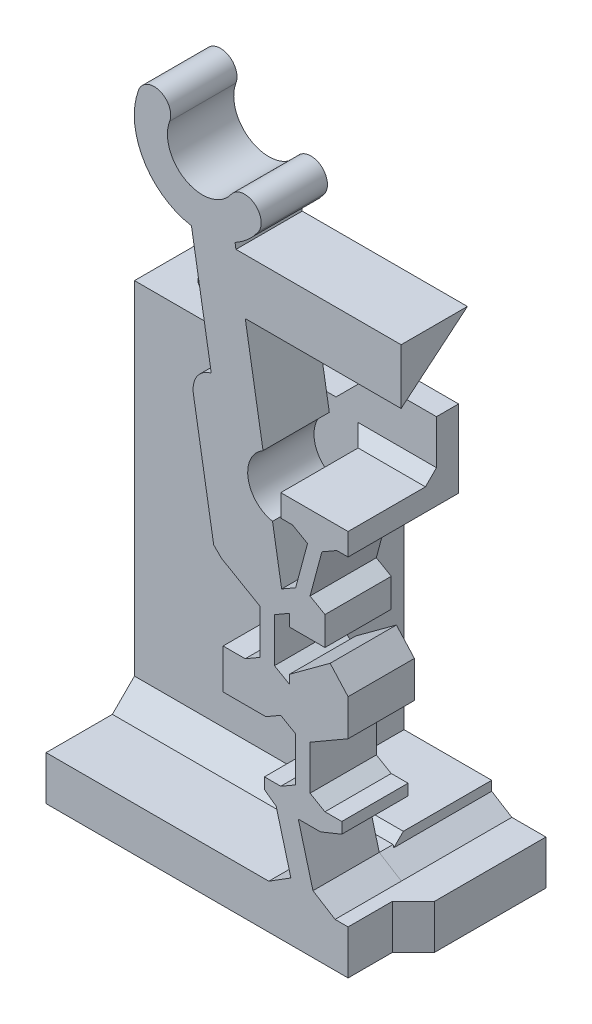
SolidWorks part; units mm, degrees
material "Nylon 6/12"
ref_plane "Front Plane" through (0, 0, 0) normal (0, 0, 1) x (1, 0, 0)
ref_plane "Top Plane" through (0, 0, 0) normal (0, 1, 0) x (1, 0, 0)
ref_plane "Right Plane" through (0, 0, 0) normal (1, 0, 0) x (0, 0, -1)
sketch "Sketch-SkeletonConfigUp" plane through (0, 0, 0) normal (0, 0, 1) x (1, 0, 0)
  line L0 (0, 0) -> (0, -50000) construction
  line L1 (0, 0) -> (4.5811, 6.2164) construction
  line L2 (9.8143, 13.3177) -> (4.5811, 13.945) construction
  line L3 (4.5811, 13.945) -> (2.9713, 10.4094) construction
  line L4 (2.9713, 10.4094) -> (4.5811, 6.2164) construction
  line L5 (4.5811, 13.945) -> (6.2429, 19.1409) construction
  line L6 (2.9713, 10.4094) -> (0.0405, 27.8193) construction
  line L7 (4.5811, 6.2164) -> (9.8143, 13.3177) construction
  line L8 (-587.3593, -797.0242) -> (9.8143, 13.3177) construction
  dimension "D2" = 7.7221
  dimension "D3" = 8.8212
  dimension "D4" = 5.2707
  dimension "D5" = 119.553
  dimension "D6" = 3.8848
  dimension "D7" = 5.4552
  dimension "D8" = 17.6549
  dimension "D9" = 4.4914
  dimension "D10" = 6.745
  dimension "D11" = 145.964
  dimension "D12" = 143.612
sketch "Sketch-SkeletonConfigDown" plane through (0, 0, 0) normal (0, 0, 1) x (1, 0, 0)
  line L0 (0, 0) -> (0, -50000) construction
  line L1 (0, 0) -> (4.5811, 6.2164) construction
  line L2 (9.8143, 13.3177) -> (4.5811, 13.945) construction
  line L3 (4.5811, 13.945) -> (6.1909, 10.4094) construction
  line L4 (6.1909, 10.4094) -> (4.5811, 6.2164) construction
  line L5 (4.5811, 13.945) -> (1.753, 18.6098) construction
  line L6 (6.1909, 10.4094) -> (-8.8652, 19.6294) construction
  line L7 (4.5811, 6.2164) -> (9.8143, 13.3177) construction
  line L8 (-589.9357, -800.5203) -> (9.8143, 13.3177) construction
  dimension "D2" = 7.7221
  dimension "D3" = 8.8212
  dimension "D4" = 5.2707
  dimension "D5" = 119.553
  dimension "D6" = 3.8848
  dimension "D7" = 5.4552
  dimension "D8" = 17.6549
  dimension "D9" = 4.4914
  dimension "D10" = 6.745
  dimension "D11" = 145.964
  dimension "D1" = 143.612
ref_plane "Plane-Cam Base" through (9.128, 0, 0) normal (1, 0, 0) x (0, 0, -1)
ref_plane "Plane-Down-to-Up Derailleur Clearance" through (6.628, 0, 0) normal (1, 0, 0) x (0, 0, -1)
ref_plane "Plane-Cam Cavity Roof" through (5.128, 0, 0) normal (1, 0, 0) x (0, 0, -1)
sketch "Sketch-SwitchBossUp" plane through (0, 0, 0) normal (0, 0, 1) x (1, 0, 0)
  line L0 (3.5811, 11.4759) -> (3.5811, 12.945) construction
  line L5 (5.5811, 12.5552) -> (5.5811, 11.263)
  line L7 (1.5115, 25.1048) -> (1.5536, 24.8548)
  line L8 (-0.4607, 24.7728) -> (0.4359, 19.4465)
  line L9 (2.9713, 10.4094) -> (0.0405, 27.8193) construction
  line L11 (0.1364, 21.2256) -> (2.1086, 21.5576) construction
  line L15 (6.628, -23.7286) -> (6.628, 23.7286) construction
  line L16 (2.9713, 10.4094) -> (4.5811, 6.2164) construction
  line L17 (3.5811, 12.945) -> (3.5811, 14.945) construction
  line L18 (5.5811, 12.945) -> (5.5811, 14.945) construction
  line L19 (4.2561, 13.945) -> (4.9061, 13.945) construction
  line L20 (3.5811, 14.945) -> (5.5811, 14.945) construction
  line L21 (3.5811, 12.945) -> (5.5811, 12.945) construction
  line L22 (4.5811, 12.945) -> (4.5811, 14.945) construction
  line L23 (4.5811, 6.2164) -> (8.5405, 7.1023) construction
  line L24 (1.9713, 9.4094) -> (1.9713, 11.4094) construction
  line L25 (3.9713, 9.4094) -> (3.9713, 11.4094) construction
  line L26 (3.9713, 9.4094) -> (1.9713, 9.4094) construction
  line L27 (1.9713, 11.4094) -> (3.9713, 11.4094) construction
  line L28 (3.5811, 7.2164) -> (5.5811, 7.2164) construction
  line L29 (3.5811, 7.2164) -> (3.5811, 5.2164) construction
  line L30 (5.5811, 7.2164) -> (5.5811, 5.2164) construction
  line L31 (3.5811, 5.2164) -> (5.5811, 5.2164) construction
  line L32 (4.9061, 6.2164) -> (4.2561, 6.2164) construction
  line L40 (3.2963, 10.4094) -> (2.6463, 10.4094) construction
  line L66 (0.0405, 27.8193) -> (0.0405, 50027.8193) construction
  line L74 (0.5455, 12.7717) -> (-0.3728, 18.2264)
  line L75 (0.3841, 13.7302) -> (2.3564, 14.0622) construction
  line L76 (5.5811, 11.263) -> (5.5811, 12.5552) construction
  line L77 (5.5811, 7.6061) -> (6.628, 8.2105)
  line L80 (5.8152, 10.763) -> (6.628, 9.8603)
  line L81 (9.128, 1033.2419) -> (9.128, 20.0586) construction
  line L85 (6.9307, 9.5241) -> (8.5405, 7.7363) construction
  line L88 (5.7256, 16.3347) -> (6.628, 16.3347)
  line L92 (3.7762, 8.3129) -> (6.9307, 9.5241) construction
  line L97 (3.2085, 15.0241) -> (3.6203, 12.5779)
  line L98 (1.9713, 9.0197) -> (0.9713, 9.0197)
  line L99 (0.9713, 9.0197) -> (0.9713, 7.2164)
  line L100 (0.9713, 7.2164) -> (2.9061, 7.2164)
  line L101 (4.5811, 6.2164) -> (6.9307, 9.5241) construction
  line L103 (0.0405, 27.8193) -> (1.9448, 26.4638) construction
  line L104 (6.9307, 9.5241) -> (8.5405, 7.7363) construction
  line L107 (1.9713, 9.4094) -> (1.9713, 9.0197) construction
  line L109 (0.0405, 27.8193) -> (-2.1498, 28.6358) construction
  line L111 (6.628, 9.8603) -> (6.628, 8.2105)
  line L112 (6.628, 9.8603) -> (6.9307, 9.5241) construction
  line L113 (2.8424, 4.8267) -> (2.8424, 4.3267)
  line L114 (7.3693, 7.7363) -> (7.3563, 7.7363) construction
  line L121 (5.0383, -1.1653) -> (5.0383, 1.4614) construction
  line L122 (2.7784, 17.579) -> (3.2085, 15.0241) construction
  line L127 (5.5811, 15.3347) -> (5.5811, 14.945) construction
  line L130 (6.0388, 0.837) -> (6.628, 0.837)
  line L132 (2.8424, 4.3267) -> (3.3749, 3.937)
  line L133 (2.9713, 10.4094) -> (6.1909, 10.4094) construction
  line L134 (4.5811, 10.4094) -> (4.5811, 13.945) construction
  line L135 (4.5811, 10.4094) -> (4.5811, 6.2164) construction
  line L136 (0.8973, 12.4192) -> (0.5455, 12.7717)
  line L137 (3.9713, 9.4094) -> (5.5811, 7.2164) construction
  line L139 (5.8152, 10.763) -> (3.9713, 9.4094)
  line L141 (4.0386, 1.4604) -> (3.0388, 0.8347)
  line L142 (3.0388, 0.8347) -> (3.0388, -1.1653)
  line L143 (9.128, 20.0586) -> (9.128, 18.3333) construction
  line L145 (9.128, 16.6071) -> (9.128, -49992.4167) construction
  line L147 (5.5811, 11.263) -> (5.5811, 12.5552) construction
  line L150 (3.0388, -1.1653) -> (5.0383, -1.1653)
  line L151 (3.3749, 3.937) -> (4.3749, 3.937) construction
  line L152 (4.792, 14.945) -> (4.2561, 12.945)
  line L153 (5.442, 14.945) -> (4.9061, 12.945)
  line L157 (3.5811, 16.3347) -> (3.5811, 15.3347)
  line L158 (6.117, 15.3347) -> (6.628, 15.3347)
  line L162 (3.2963, 11.4094) -> (3.2963, 9.4094)
  line L164 (2.6463, 11.4094) -> (2.6463, 9.4094)
  line L169 (4.2561, 7.2164) -> (4.2561, 5.2164)
  line L170 (4.9061, 5.2164) -> (4.9061, 7.2164)
  line L175 (4.2561, 7.2164) -> (3.5811, 7.6061)
  line L176 (4.9061, 7.2164) -> (5.5811, 7.6061)
  line L177 (5.5811, 7.2164) -> (5.5811, 7.6061) construction
  line L179 (4.2561, 5.2164) -> (3.5811, 4.8267)
  line L180 (3.5811, 5.2164) -> (3.5811, 4.8267) construction
  line L181 (3.5811, 4.8267) -> (2.8424, 4.8267)
  line L183 (4.9061, 5.2164) -> (5.5811, 4.8267)
  line L184 (5.5811, 5.2164) -> (5.5811, 4.8267) construction
  line L186 (9.128, -23.7286) -> (9.128, 23.7286) construction
  line L187 (2.6463, 9.4094) -> (1.9713, 9.0197)
  line L188 (3.2963, 9.4094) -> (3.9713, 9.0197)
  line L189 (3.2963, 11.4094) -> (3.9713, 11.7991)
  line L190 (2.6463, 11.4094) -> (0.8973, 12.4192)
  line L191 (3.9713, 11.4094) -> (3.9713, 11.7991) construction
  line L192 (3.9713, 11.7991) -> (3.9713, 11.263)
  line L193 (4.9061, 12.945) -> (5.5811, 12.5552)
  line L194 (4.2561, 12.945) -> (3.6203, 12.5779)
  line L195 (3.9713, 11.263) -> (5.5811, 11.263)
  line L196 (3.9713, 9.4094) -> (3.9713, 9.0197)
  line L197 (3.5811, 7.2164) -> (3.5811, 7.6061) construction
  line L199 (3.5811, 7.6061) -> (2.9061, 7.2164)
  line L201 (2.8424, 4.3267) -> (2.8424, 3.937) construction
  line L202 (2.8424, 3.937) -> (3.3749, 3.937) construction
  line L204 (5.0383, 1.437) -> (3.0388, 1.437) construction
  line L205 (3.0388, 1.437) -> (3.0388, 0.8347) construction
  line L206 (5.0383, 1.4614) -> (6.0388, 0.837)
  line L207 (9.128, 18.3333) -> (9.128, 16.6071) construction
  line L208 (6.628, -1.1653) -> (6.628, 0.837)
  line L209 (9.128, 20.0586) -> (9.128, 16.6071) construction
  line L211 (5.0383, 1.4614) -> (4.3749, 3.937)
  line L212 (4.0386, 1.4604) -> (3.3749, 3.937)
  line L214 (4.792, 14.945) -> (4.1169, 15.3347)
  line L215 (4.1169, 15.3347) -> (3.5811, 15.3347)
  line L216 (5.442, 14.945) -> (6.117, 15.3347)
  line L217 (5.5811, 12.945) -> (5.5811, 12.5552) construction
  line L218 (5.442, 14.945) -> (5.442, 15.3347) construction
  line L219 (6.117, 15.3347) -> (4.1169, 15.3347) construction
  line L221 (9.028, 22.3548) -> (9.028, 24.8548)
  line L224 (3.5811, 16.3347) -> (5.7256, 16.3347)
  line L232 (6.628, 15.3347) -> (6.628, 16.3347)
  line L233 (6.628, -1.1653) -> (5.0383, -1.1653)
  line L236 (1.5536, 24.8548) -> (9.028, 24.8548)
  line L240 (4.3749, 3.937) -> (5.3749, 3.937)
  line L241 (5.3749, 3.937) -> (6.3424, 4.3267)
  line L248 (9.028, 22.3548) -> (1.9744, 22.3548)
  line L249 (1.9744, 22.3548) -> (2.7784, 17.579)
  line L367 (5.5811, 4.8267) -> (6.3424, 4.8267)
  line L368 (6.3424, 4.8267) -> (6.3424, 4.3267)
  arc A0 (1.5115, 25.1048) -> (2.5558, 26.0289) centre (0.0405, 27.8193) ccw
  arc A1 (-0.4607, 24.7728) -> (-2.8525, 28.8978) centre (0.0405, 27.8193) cw
  arc A2 (-2.8525, 28.8978) -> (-1.447, 28.3738) centre (-2.1498, 28.6358) cw
  arc A3 (2.5558, 26.0289) -> (1.3338, 26.8987) centre (1.9448, 26.4638) ccw
  arc A4 (-1.447, 28.3738) -> (1.3338, 26.8987) centre (0.0405, 27.8193) ccw
  arc A5 (3.5811, 12.945) -> (3.5811, 14.945) centre (3.1778, 13.945) ccw construction
  arc A6 (5.5811, 12.945) -> (5.5811, 14.945) centre (5.9843, 13.945) cw construction
  arc A7 (2.5293, 9.921) -> (1.9713, 11.4094) centre (1.568, 10.4094) ccw construction
  arc A8 (3.9713, 11.4094) -> (3.9713, 9.4094) centre (4.3745, 10.4094) ccw construction
  arc A9 (3.5811, 7.2164) -> (3.5811, 5.2164) centre (3.1779, 6.2164) cw construction
  arc A10 (5.5811, 7.2164) -> (5.5811, 5.2164) centre (5.9844, 6.2164) ccw construction
  arc A19 (-0.3728, 18.2264) -> (0.4359, 19.4465) centre (0.6836, 18.4042) cw
  circle A28 centre (0.0405, 27.8193) radius 2.3375 construction
  arc A29 (1.9713, 9.4094) -> (2.5293, 9.921) centre (1.568, 10.4094) ccw construction
  arc A37 (3.2085, 15.0241) -> (2.7784, 17.579) centre (3.4651, 16.381) cw
  point P53 (4.5811, 13.945)
  point P63 (2.9713, 10.4094)
  point P93 (1.1225, 21.3916)
  dimension "D23" = 1.5875
  dimension "D24" = 0.75
  dimension "D7" = 1.3809
  dimension "D2" = 2
  dimension "D5" = 2
  dimension "D6" = 0.65
  dimension "D8" = 42
  dimension "D16" = 42
  dimension "D27" = 120
  dimension "D28" = 120
  dimension "D29" = 120
  dimension "D30" = 120
  dimension "D31" = 120
  dimension "D32" = 120
  dimension "D33" = 120
  dimension "D34" = 120
  dimension "D17" = 0.5
  dimension "D21" = 1
  dimension "D9" = 17.5
  dimension "D22" = 1
  dimension "D38" = 2
  dimension "D39" = 0.5
  dimension "D40" = 60
  dimension "D41" = 1
  dimension "D42" = 45
  dimension "D43" = 120
  dimension "D10" = 15
  dimension "D12" = 2.5
  dimension "D13" = 1
  dimension "D19" = 1
  dimension "D25" = 15
  dimension "D26" = 120
  dimension "D35" = 120
  dimension "D20" = 3
  dimension "D48" = 2
  dimension "D49" = 0.6
  dimension "D82" = 1
  dimension "D83" = 3.5
  dimension "D14" = 2.5
  dimension "D15" = 0.25
extrude "Boss-Switch Body" add sketch "Sketch-SwitchBossUp" along normal blind 3
sketch "Sketch1" plane through (0, 0, 0) normal (0, 0, -1) x (-1, 0, 0)
  line L1 (-7.5811, -1.1653) -> (0.4122, -1.1653)
  line L2 (-7.5811, -1.1653) -> (-7.5811, 0.837)
  line L4 (0.4122, -1.1653) -> (0.4122, 0.8347)
  line L5 (-3.5811, 18.8347) -> (-7.5811, 18.8347)
  line L10 (-7.5811, 18.8347) -> (-7.5811, 15.3347)
  line L11 (-4.0386, 1.4604) -> (-5.0386, 1.4604)
  line L12 (-7.5811, 15.3347) -> (-3.5811, 15.3347)
  line L13 (-4.0386, 1.4604) -> (-3.0388, 0.8347)
  line L14 (-3.5811, 15.3347) -> (-3.5811, 18.8347)
  line L20 (-4.3749, 3.937) -> (-5.0383, 1.4614) construction
  line L22 (-3.0388, -1.1653) -> (-6.628, -1.1653) construction
  line L23 (-3.0388, 0.8347) -> (0.4122, 0.8347)
  line L24 (-5.0386, 1.4604) -> (-6.0388, 0.837)
  line L25 (-6.0388, 0.837) -> (-7.5811, 0.837)
  dimension "D1" = 3.5
extrude "Boss-Flange Width" add sketch "Sketch1" along normal blind 5
ref_plane "Plane-Sta2Sit Groove" through (0.0405, 0, 0) normal (1, 0, 0) x (0, 0, -1)
ref_plane "Plane-Cam Outer Surface" through (-12.0395, 0, 0) normal (1, 0, 0) x (0, 0, -1)
ref_plane "Plane-FlangeTop" through (-7.0395, 0, 0) normal (1, 0, 0) x (0, 0, -1)
sketch "Sketch2" plane through (-7.0395, 0, 0) normal (1, 0, 0) x (0, 0, -1)
  line L0 (5, 15.3347) -> (-3, 15.3347) construction
  line L1 (5, 17.3347) -> (1, 17.3347)
  line L2 (5, 17.3347) -> (5, 15.3347)
  line L3 (5, 15.3347) -> (1, 15.3347)
  line L4 (1, 17.3347) -> (1, 15.3347)
  line L5 (-3, -1.1653) -> (-3, 0.837) construction
  line L11 (5, 0.8347) -> (-3, 0.8347)
  line L12 (5, 0.8347) -> (5, -1.1653)
  line L13 (5, -1.1653) -> (-3, -1.1653)
  line L14 (-3, 0.8347) -> (-3, -1.1653)
  line L15 (0, 10.4094) -> (0, 27.8193) construction
  line L17 (5, 0.837) -> (5, -1.1653) construction
  line L18 (-3, 0.8347) -> (0, 0.8347) construction
  dimension "D1" = 1
  dimension "D2" = 2
extrude "Boss-Flange Height" add sketch "Sketch2" along normal up to surface (11.6675 mm away)
sketch "Sketch24" plane through (0, 0, 0) normal (0, 0, 1) x (1, 0, 0)
  line L0 (3.5811, 16.3347) -> (7.5811, 16.3347)
  line L1 (7.5811, 18.8347) -> (7.5811, 15.3347) construction
  line L2 (3.5811, 16.3347) -> (3.5811, 18.8347)
  line L3 (3.5811, 18.8347) -> (7.5811, 18.8347)
  line L4 (7.5811, 18.8347) -> (7.5811, 16.3347)
  point P5 (3.5811, 18.8347)
extrude "Cut-Wall Clearance" cut sketch "Sketch24" against normal up to surface (1 mm away) up to face at (-1.7292, 16.3347, -1)
sketch "Sketch10" plane through (0, 15.3347, 0) normal (0, 1, 0) x (1, 0, 0)
  line L0 (9.128, -23.7286) -> (9.128, 23.7286) construction
  line L1 (7.5811, 5) -> (5.128, 5)
  line L2 (7.5811, 5) -> (7.5811, 2)
  line L3 (7.5811, 2) -> (5.128, 2)
  line L5 (4.628, 7) -> (4.628, 1) construction
  line L6 (3.5811, 1) -> (-7.0395, 1) construction
  line L8 (5.128, 5) -> (5.128, 2)
  dimension "D1" = 1
  dimension "D2" = 0.5
  dimension "D3" = 4.5
extrude "Cut-Up-To-Down Derailleur Clearance" cut sketch "Sketch10" along normal up to next
sketch "Sketch17" plane through (0, 15.3347, 0) normal (0, -1, 0) x (1, 0, 0)
  line L0 (5.128, -5) -> (-7.0395, -5)
  line L1 (5.128, -5) -> (-7.0395, -5) construction
  line L2 (-7.0395, -5) -> (-7.0395, -1)
  line L3 (-7.0395, -1) -> (5.128, -1)
  line L4 (5.128, -1) -> (5.128, -5)
  line L5 (-7.0395, -1) -> (-7.0395, -5) construction
extrude "Boss-Flange Support" add sketch "Sketch17" along normal up to surface (14.5 mm away) up to face at (-2.0003, 0.8347, -1)
sketch "Sketch-HolePositions" plane through (0, -1.1653, 0) normal (0, -1, 0) x (1, 0, 0)
  line L0 (-7.0395, -3) -> (7.5811, -3) construction
  line L1 (7.5811, -5) -> (-7.0395, -5) construction
  line L2 (7.5811, -5) -> (7.5811, 0) construction
  line L4 (-7.0395, -22.2167) -> (-7.0395, 22.2167) construction
  point P6 (-5.0395, -3)
  point P7 (-0.5395, -3)
  dimension "D1" = 2
  dimension "D2" = 4.5
  dimension "D3" = 2
sketch "Sketch6" plane through (0, -1.1653, 0) normal (0, -1, 0) x (-1, 0, 0)
  point P0 (5.0395, 3)
  point P3 (0.5395, 3)
hole_wizard "Tap Drill for M2x0.4 Tap1" positions "Sketch6" profile "Sketch5" hole size "M2x0.4" standard "ANSI Metric" end condition through all
sketch "Sketch5" plane through (-5.0395, -1.1653, -3) normal (1, 0, 0) x (0, 0, -1)
  line L0 (0, 0) -> (0, 30.5511)
  line L1 (0, 30.5511) -> (0.8, 30.5511)
  line L2 (0.8, 30.5511) -> (0.8, 0)
  line L5 (0.8, 0) -> (0, 0)
  line L11 (0, -6.35) -> (0, 107.95) construction
  dimension "Thru Hole Dia." = 1.6
  dimension "Thru Hole Depth" = 30.5511
sketch "Sketch9" plane through (0, -1.1653, 0) normal (0, -1, 0) x (1, 0, 0)
  point P0 (-5.0395, -3)
  point P3 (-0.5395, -3)
hole_wizard "M2 Clearance Hole2" positions "Sketch9" profile "Sketch8" hole size "M2" standard "ANSI Metric"
sketch "Sketch8" plane through (-5.0395, -1.1653, -3) normal (1, 0, 0) x (0, 0, -1)
  line L0 (0, 0) -> (0, 15.721)
  line L1 (0, 15.721) -> (1.2, 15)
  line L2 (1.2, 15) -> (1.2, 0)
  line L5 (1.2, 0) -> (0, 0)
  line L10 (0, 15.721) -> (-1.2, 15) construction
  line L11 (0, -6.35) -> (0, 107.95) construction
  dimension "Hole Dia." = 2.4
  dimension "Hole Depth" = 15
  dimension "Drill Angle" = 118
sketch "Sketch-Measurements for Derailleur Ramps" [suppressed] plane through (0, 0, 0) normal (0, 0, 1) x (1, 0, 0)
  line L0 (3.184, 15.1695) -> (2.4687, 19.4188)
  line L1 (2.8264, 17.2941) -> (1.8402, 17.1281)
  line L2 (2.9713, 10.4094) -> (0.0405, 27.8193) construction
  line L3 (1.8402, 17.1281) -> (-1.3081, 15.0016)
  line L4 (6.1909, 10.4094) -> (-8.8652, 19.6294) construction
  line L5 (1.8402, 17.1281) -> (2.6012, 12.6077)
  line L6 (2.6012, 12.6077) -> (-1.3081, 15.0016)
  line L7 (0.2661, 16.0649) -> (0.2661, 17.1281)
  line L8 (0.2661, 17.1281) -> (1.8402, 17.1281)
  line L9 (6.1909, 10.4094) -> (2.9713, 10.4094)
  line L10 (5.386, 8.3129) -> (3.7762, 8.3129)
  line L11 (2.6116, 18.5698) -> (1.5115, 25.1048) construction
  line L12 (6.1909, 10.4094) -> (4.5811, 6.2164) construction
  line L13 (4.5811, 8.3129) -> (4.5811, 8.7912)
  line L14 (4.5811, 6.2164) -> (5.386, 8.3129)
  line L15 (2.9713, 10.4094) -> (4.5811, 6.2164) construction
  line L16 (3.7762, 8.3129) -> (4.5811, 6.2164)
  line L17 (5.386, 8.3129) -> (5.386, 8.7912)
  dimension "D1" = 1.5742
  dimension "D2" = 0.8049
ref_plane "Plane1" through (0, 7.1023, 0) normal (0, 1, 0) x (1, 0, 0)
ref_plane "Plane-Cantilever Cut" [suppressed] through (7.0848, 8.5204, -1.9058) normal (-0.6301, -0.7578, 0.1695) x (-0.7765, 0.6151, -0.1368)
sketch "Sketch14" [suppressed] plane through (7.0848, 8.5204, -1.9058) normal (-0.6301, -0.7578, 0.1695) x (-0.7765, 0.6151, -0.1368)
  line L0 (2.3023, -1.6911) -> (-0.3551, -1.6911)
  line L2 (2.3023, -4.3362) -> (2.3023, -1.6911)
  line L3 (-0.3551, -1.6911) -> (-0.3551, -4.4608)
  line L5 (-0.3551, -4.4608) -> (1.0087, -5.0843)
  line L6 (1.0087, -5.0843) -> (2.3023, -4.3362)
extrude "Cut-Down-to-Up Cantilever Slope" [suppressed] cut sketch "Sketch14" against normal up to next
ref_plane "Plane-Symmetry Plane" through (0, 0, 1.5) normal (0, 0, 1) x (1, 0, 0)
sketch "Sketch-Cable Center Point" plane through (0, 0, 1.5) normal (0, 0, 1) x (1, 0, 0)
  line L0 (0.0405, 27.8193) -> (0.1722, 27.0366)
  line L1 (2.9713, 10.4094) -> (0.0405, 27.8193) construction
  point P0 (0.0405, 27.8193)
  dimension "D1" = 0.7937
chamfer "Chamfer-Flange Support" distance 1.5 angle 45 1 edges at (3.5811, 17.3347, -3)
chamfer "Chamfer-Flange Support 2" distance 1.5 angle 45 2 edges at (5.128, 17.0847, -2) (5.128, 15.3347, -1.5)
chamfer "Chamfer-Flange Support 3" distance 1 angle 45 1 edges at (-2.0003, 0.8347, -1)
chamfer "Chamfer3" distance 0.5 angle 45 3 edges at (3.5811, 15.8347, -1) (5.1045, 15.3347, -1) (5.5811, 16.3347, -1)
chamfer "Chamfer7" [suppressed] distance 1 angle 45
sketch "Sketch23" plane through (0, 0, -1) normal (0, 0, 1) x (1, 0, 0)
  line L0 (5.128, 1.8347) -> (1.1605, 1.8347)
  line L1 (-7.0395, 1.8347) -> (5.128, 1.8347) construction
  line L2 (1.1605, 1.8347) -> (1.1605, 13.8347)
  line L3 (1.1605, 13.8347) -> (5.128, 13.8347)
  line L4 (5.128, 13.8347) -> (5.128, 1.8347)
  line L5 (0.6605, -1.1653) -> (0.6605, 13.8347) construction
  dimension "D1" = 0.5
extrude "Cut-Gap for Printing" cut sketch "Sketch23" against normal through all
sketch "Sketch25" plane through (0, 0, 0) normal (0, 0, 1) x (1, 0, 0)
  line L0 (6.628, 15.3347) -> (7.5811, 15.3347)
  line L1 (7.5811, 15.3347) -> (7.5811, 18.8347)
  line L2 (7.5811, 18.8347) -> (6.628, 18.8347)
  line L3 (6.628, -23.7286) -> (6.628, 23.7286) construction
  line L4 (7.5811, 18.8347) -> (3.5811, 18.8347) construction
  line L5 (6.628, 18.8347) -> (6.628, 15.3347)
extrude "Cut-Derailleur Clearance" cut sketch "Sketch25" against normal through all
chamfer "Chamfer8" distance 1 angle 45 1 edges at (6.628, -0.1641, 0)
ref_plane "Plane2" through (-5.9548, 8.4004, 7.0004) normal (0.4783, -0.6747, -0.5622) x (-0.8782, -0.3674, -0.3062)
sketch "Sketch26" plane through (-5.9548, 8.4004, 7.0004) normal (0.4783, -0.6747, -0.5622) x (-0.8782, -0.3674, -0.3062)
  line L0 (-12.9549, 15.9117) -> (-12.9549, 12.0065)
  line L1 (-17.0603, 15.9117) -> (-10.4961, 15.9117) construction
  line L2 (-10.8657, 12.0065) -> (-17.0603, 12.0065) construction
  line L3 (-12.9549, 12.0065) -> (-20.0302, 12.0065)
  line L4 (-20.0302, 12.0065) -> (-20.0302, 15.9117)
  line L5 (-20.0302, 15.9117) -> (-12.9549, 15.9117)
extrude "Cut-Extrude1" cut sketch "Sketch26" along normal up to next
sketch "Sketch27" plane through (5.128, 0, 0) normal (1, 0, 0) x (0, 0, -1)
  line L0 (3.5, 18.8347) -> (3.5, 13.8347) construction
  line L1 (3, 18.8347) -> (5, 18.8347)
  line L2 (3, 18.8347) -> (3, 13.8347)
  line L3 (3, 13.8347) -> (5, 13.8347)
  line L4 (5, 18.8347) -> (5, 13.8347)
  dimension "D1" = 0.5
extrude "Cut-Wide Derailleur Clearance" cut sketch "Sketch27" against normal blind 4 and the other way through all
chamfer "Chamfer9" distance 1 angle 45 1 edges at (4.6045, 18.8347, -3)
equation "\"axle-diameter\"=2"
equation "\"switch-thickness\"=12"
equation "\"base-width\"=4.0"
equation "\"axle-bushing-radius\"=3"
equation "\"clearance\"= 0.25"
equation "\"arm-width\"=1.5"
equation "\"min-diameter\"=70"
equation "\"alpha\"=143.6120"
equation "\"gamma\"=119.5526"
equation "\"delta\"=145.9637"
equation "\"epsilon\"=6.7452"
equation "\"l_AB\"=8.8212"
equation "\"l_AC\"=4.4914"
equation "\"l_BD\"=5.2707"
equation "\"l_CD\"=3.8848"
equation "\"l_CE\"=17.6549"
equation "\"l_DF\"=5.4552"
equation "\"l_OA\"=7.7221"
equation "\"D2@Sketch-SkeletonConfigUp\" = \"l_OA\""
equation "\"D3@Sketch-SkeletonConfigUp\" = \"l_AB\""
equation "\"D4@Sketch-SkeletonConfigUp\" = \"l_BD\""
equation "\"D5@Sketch-SkeletonConfigUp\" = \"gamma\""
equation "\"D6@Sketch-SkeletonConfigUp\" = \"l_CD\""
equation "\"D7@Sketch-SkeletonConfigUp\" = \"l_DF\""
equation "\"D8@Sketch-SkeletonConfigUp\" = \"l_CE\""
equation "\"D9@Sketch-SkeletonConfigUp\" = \"l_AC\""
equation "\"D_groove\"=3.175"
equation "\"D7@Sketch-SkeletonConfigDown\" = \"l_DF\""
equation "\"D6@Sketch-SkeletonConfigDown\" = \"l_CD\""
equation "\"D2@Sketch-SkeletonConfigDown\" = \"l_OA\""
equation "\"D3@Sketch-SkeletonConfigDown\" = \"l_AB\""
equation "\"D9@Sketch-SkeletonConfigDown\" = \"l_AC\""
equation "\"D8@Sketch-SkeletonConfigDown\" = \"l_CE\""
equation "\"D5@Sketch-SkeletonConfigDown\" = \"gamma\""
equation "\"D4@Sketch-SkeletonConfigDown\" = \"l_BD\""
equation "\"D1@Sketch-SkeletonConfigDown\" = \"alpha\""
equation "\"hinge_length\"=1.5"
equation "\"hinge_depth\"=0.25"
equation "\"D10@Sketch-SkeletonConfigUp\"=\"epsilon\""
equation "\"D11@Sketch-SkeletonConfigUp\"=\"delta\""
equation "\"D12@Sketch-SkeletonConfigUp\"=\"alpha\""
equation "\"D11@Sketch-SkeletonConfigDown\"=\"delta\""
equation "\"D10@Sketch-SkeletonConfigDown\"=\"epsilon\""
equation "\"EE_dx\"=8.9056"
equation "\"EE_dy\"=8.1898"
equation "\"r_groove\"=\"D_groove\"/2"
equation "\"t_wall\"=25.4/16"
equation "\"width_lower\"=\"D_groove\"+\"t_wall\""
equation "\"cable_to_bottom\"=30.6257"
equation "\"switch_EE-up_base_dy\"=24"
equation "\"switch_EE-down_base_dy\"=16"
equation "\"D_axle\"=25.4/8"
equation "\"D_up_to_down\"=16"
equation "\"D_down_to_up\"=25"
equation "\"t_cam_base\"=7.5"
equation "\"D23@Sketch-SwitchBossUp\"=\"D_groove\"/2"
equation "\"D1@Sketch-Cable Center Point\"=\"D_groove\"/4"
